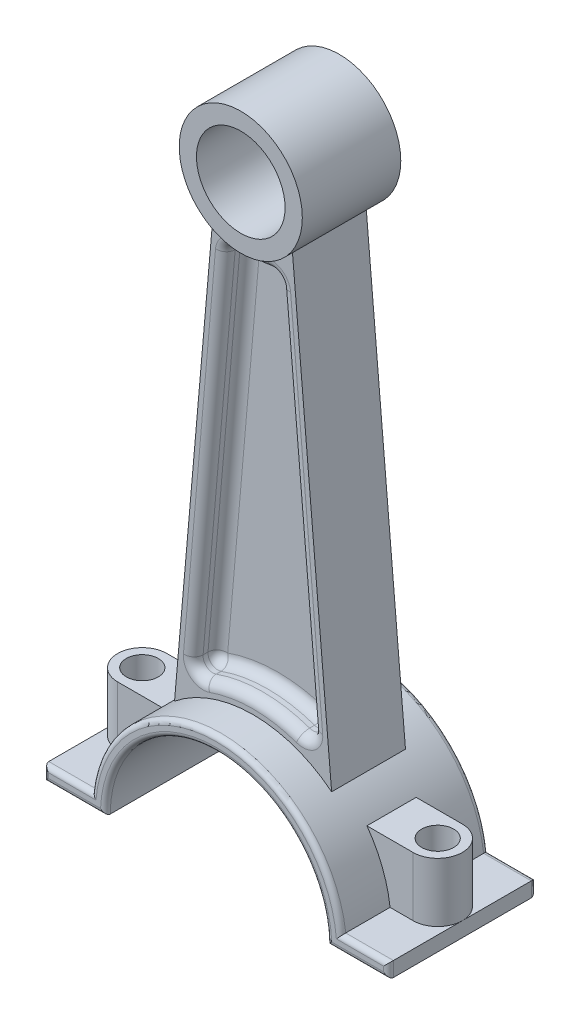
SolidWorks part; units mm, degrees
ref_plane "Front Plane" through (0, 0, 0) normal (0, 0, 1) x (1, 0, 0)
ref_plane "Top Plane" through (0, 0, 0) normal (0, 1, 0) x (1, 0, 0)
ref_plane "Right Plane" through (0, 0, 0) normal (1, 0, 0) x (0, 0, -1)
sketch "Sketch2" plane through (0, 0, 0) normal (0, 0, 1) x (1, 0, 0)
  line L0 (0, 0) -> (0, -120.4) construction
  line L1 (-35, -120.4) -> (-22.5, -120.4)
  line L2 (22.5, -120.4) -> (35, -120.4)
  line L4 (25.3229, -117.4) -> (35, -117.4)
  line L5 (-35, -117.4) -> (-25.3229, -117.4)
  line L6 (-35, -117.4) -> (-35, -120.4)
  line L7 (35, -117.4) -> (35, -120.4)
  line L8 (-8, -9.6047) -> (-15.9529, -100.5064)
  line L9 (8, -9.6047) -> (15.9529, -100.5064)
  circle A0 centre (0, 0) radius 9
  circle A1 centre (0, 0) radius 12.5
  arc A2 (22.5, -120.4) -> (-22.5, -120.4) centre (0, -120.4) ccw
  arc A4 (25.3229, -117.4) -> (-25.3229, -117.4) centre (0, -120.4) ccw
  point P9 (0, -120.4)
  dimension "D1" = 25
  dimension "D2" = 18
  dimension "D4" = 45
  dimension "D6" = 3
  dimension "D3" = 120.4
  dimension "D5" = 70
  dimension "D7" = 8
  dimension "D8" = 5
extrude "Boss-Extrude1" add sketch "Sketch2" along normal mid plane 20 contours A0 A1 region at (-5.1533, 10.9991, 0)
extrude "Boss-Extrude2" add sketch "Sketch2<3>" along normal mid plane 30 separate body contours A4 L0 A2 L2 L7 L4 | L0 A4 L5 L6 L1 A2 region at (8.3111, -96.7509, 0) region at (-0.433, -96.4, 0)
sketch "Sketch2<3>" plane through (0, 0, 0) normal (0, 0, 1) x (1, 0, 0) same geometry as "Sketch2"
extrude "Boss-Extrude3" add sketch "Sketch2<4>" along normal mid plane 15 contours A1 L0 A4 L9 | L0 A1 L8 A4 region at (6.2653, -58.5545, 0) region at (-6.2653, -58.5545, 0)
sketch "Sketch2<4>" plane through (0, 0, 0) normal (0, 0, 1) x (1, 0, 0) same geometry as "Sketch2"
sketch "Sketch3" plane through (0, 0, 0) normal (0, 0, 1) x (1, 0, 0)
  line L8 (-5.4187, -14.522) -> (-12.4385, -94.7576)
  line L9 (12.4385, -94.7576) -> (5.4187, -14.522)
  line L10 (-5.4187, -14.522) -> (-12.4385, -94.7576)
  line L11 (12.4385, -94.7576) -> (5.4187, -14.522)
  arc A8 (-5.4187, -14.522) -> (5.4187, -14.522) centre (0, 0) ccw
  arc A9 (12.4385, -94.7576) -> (-12.4385, -94.7576) centre (0, -120.4) ccw
  arc A10 (-5.4187, -14.522) -> (5.4187, -14.522) centre (0, 0) ccw
  arc A11 (12.4385, -94.7576) -> (-12.4385, -94.7576) centre (0, -120.4) ccw
  dimension "D2" = 3
extrude "Cut-Extrude1" cut sketch "Sketch3" against normal blind 5 and the other way through all from offset 7.5
mirror "Mirror1" about plane through (0, 0, 0) normal (0, 0, 1) of "Cut-Extrude1"
sketch "Sketch5" plane through (0, -117.4, 0) normal (0, 1, 0) x (1, 0, 0)
  line L0 (35, -15) -> (35, 15) construction
  line L1 (18, -5) -> (30, -5)
  line L2 (18, -5) -> (18, 5)
  line L3 (18, 5) -> (30, 5)
  line L4 (30, -5) -> (30, 5)
  line L5 (18, -5) -> (30, 5) construction
  line L6 (18, 5) -> (30, -5) construction
  circle A0 centre (30, 0) radius 5
  circle A1 centre (30, 0) radius 3.25
  point P0 (24, 0)
  line M2 (25.3229, 15) -> (25.3229, -15)
  dimension "D1" = 10
  dimension "D3" = 6.5
  dimension "D2" = 12
extrude "Boss-Extrude4" add sketch "Sketch5" against normal up to body from offset 12 contours A1 L4 A0 | L4 A1 | L4 A1 | A1 L4 A0 M2 | L3 L4 L1 L2 region at (27.2201, -117.4, 4.0225) region at (30.1118, -117.4, 4.125) region at (28.6207, -117.4, 0) region at (31.3793, -117.4, 0)
extrude "Cut-Extrude2" cut sketch "Sketch5<3>" against normal through all from surface contours L4 A1 | L4 A1 region at (28.6207, -117.4, 0) region at (31.3793, -117.4, 0) starting at face at (26.5608, -105.4, 0)
sketch "Sketch5<3>" plane through (0, -117.4, 0) normal (0, 1, 0) x (1, 0, 0) same geometry as "Sketch5"
mirror "Mirror2" about plane through (0, 0, 0) normal (1, 0, 0) of "Cut-Extrude2", "Boss-Extrude4"
fillet "Fillet4" radius 2 24 edges at (-8.9286, -54.6398, 7.5) (-8.9286, -54.6398, -7.5) (0, -15.5, -7.5) (0, -15.5, 7.5) (0, -91.9, 7.5) (-8.9286, -54.6398, -2.5) (0, -91.9, -2.5) (8.9286, -54.6398, -2.5) (0, -15.5, -2.5) (8.9286, -54.6398, 2.5) (0, -91.9, 2.5) (-8.9286, -54.6398, 2.5) (0, -15.5, 2.5) (-12.4385, -94.7576, -5) (12.4385, -94.7576, -5) (0, -91.9, -7.5) (-5.4187, -14.522, -5) (5.4187, -14.522, -5) (8.9286, -54.6398, -7.5) (8.9286, -54.6398, 7.5) (12.4385, -94.7576, 5) (5.4187, -14.522, 5) (-5.4187, -14.522, 5) (-12.4385, -94.7576, 5)
fillet "Fillet5" radius 1 16 edges at (30.1615, -117.4, 15) (35, -118.9, 15) (28.75, -120.4, 15) (0, -97.9, 15) (-28.75, -120.4, 15) (-35, -118.9, 15) (-30.1615, -117.4, 15) (0, -94.9, 15) (-30.1615, -117.4, -15) (-35, -118.9, -15) (-28.75, -120.4, -15) (0, -97.9, -15) (28.75, -120.4, -15) (35, -118.9, -15) (30.1615, -117.4, -15) (0, -94.9, -15)
